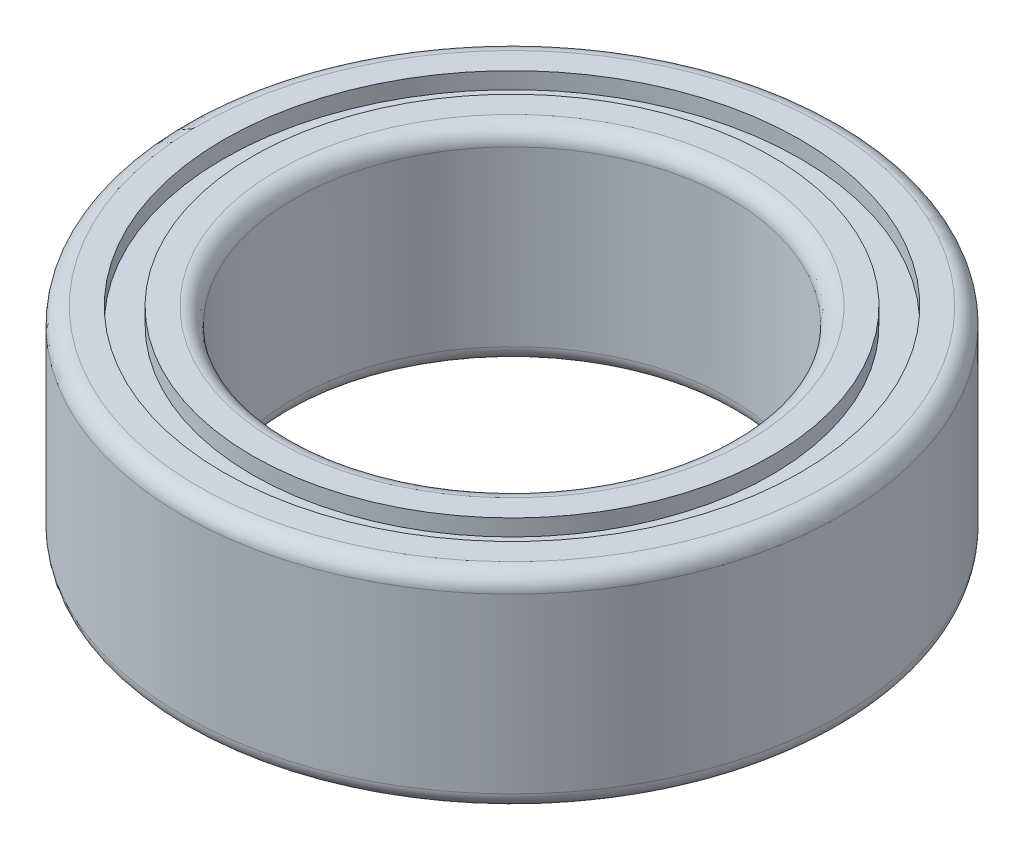
SolidWorks part; units mm, degrees
ref_plane "Front Plane" through (0, 0, 0) normal (0, 0, 1) x (1, 0, 0)
ref_plane "Top Plane" through (0, 0, 0) normal (0, 1, 0) x (1, 0, 0)
ref_plane "Right Plane" through (0, 0, 0) normal (1, 0, 0) x (0, 0, -1)
sketch "Sketch1" plane through (0, 0, 0) normal (1, 0, 0) x (0, 0, -1)
  line L0 (2.65, 1.25) -> (2.65, -1.25)
  line L1 (2.65, -1.25) -> (3.15, -1.25)
  line L2 (3.15, -1.25) -> (3.15, -1.05)
  line L3 (3.15, -1.05) -> (3.5, -1.05)
  line L4 (3.5, -1.05) -> (3.5, -1.25)
  line L5 (3.5, -1.25) -> (4, -1.25)
  line L6 (4, -1.25) -> (4, 1.25)
  line L7 (4, 1.25) -> (3.5, 1.25)
  line L8 (3.5, 1.25) -> (3.5, 1.05)
  line L9 (3.5, 1.05) -> (3.15, 1.05)
  line L10 (3.15, 1.05) -> (3.15, 1.25)
  line L11 (3.15, 1.25) -> (2.65, 1.25)
  line L12 (2.65, 0) -> (0, 0) construction
  line L13 (0, 1.1937) -> (0, 0) construction
  dimension "D1" = 8
  dimension "D2" = 5.3
  dimension "D3" = 0.5
  dimension "D4" = 0.2
  dimension "D5" = 2.5
revolve "Revolve1" add sketch "Sketch1" angle 360 about L13
fillet "Fillet1" radius 0.2 4 edges at (0, 1.25, 2.65) (0, -1.25, 2.65) (0, -1.25, 4) (0, 1.25, 4)
sketch "Sketch2" plane through (0, -1.05, 0) normal (0, -1, 0) x (1, 0, 0)
  circle A1 centre (0, 0) radius 3.15 construction
  circle A2 centre (0, 0) radius 3.5
  circle A3 centre (0, 0) radius 3.5
  circle A4 centre (0, 0) radius 3.15
  dimension "D1" = 0
extrude "Boss-Extrude1" add sketch "Sketch2" along normal up to surface (0.2 mm away) up to face at (0, -1.25, 3.8)
ref_axis "Axis1" through (0, -2.3225, 0) along (0, 1, 0)
